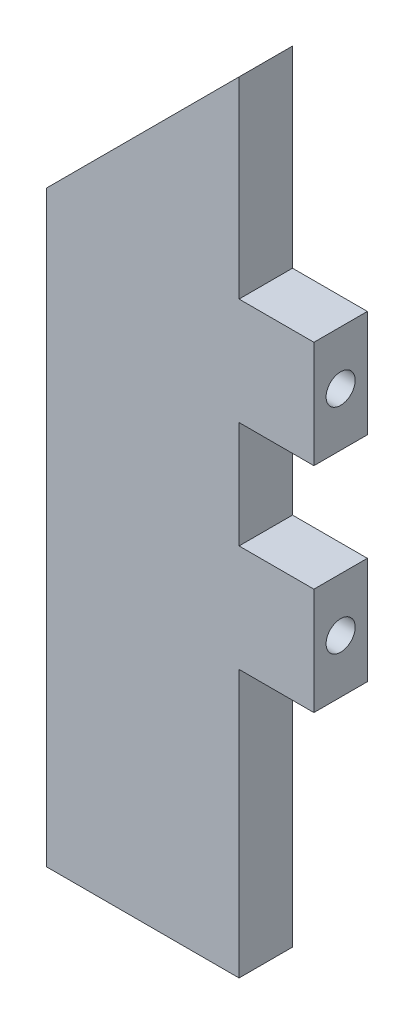
SolidWorks part; units mm, degrees
ref_plane "Front Plane" through (0, 0, 0) normal (0, 0, 1) x (1, 0, 0)
ref_plane "Top Plane" through (0, 0, 0) normal (0, 1, 0) x (1, 0, 0)
ref_plane "Right Plane" through (0, 0, 0) normal (1, 0, 0) x (0, 0, -1)
sketch "Sketch1" plane through (0, 0, 0) normal (0, 1, 0) x (1, 0, 0)
  line L1 (0, 0) -> (31.75, 0)
  line L2 (0, 0) -> (0, 6.35)
  line L3 (0, 6.35) -> (31.75, 6.35)
  line L4 (31.75, 0) -> (31.75, 6.35)
  dimension "D1" = 31.75
  dimension "D2" = 6.35
extrude "Boss-Extrude1" add sketch "Sketch1" along normal blind 101.6
chamfer "Chamfer1" distance 31.75 angle 45 1 edges at (0, 101.6, -3.175)
hole_wizard "#8-32 Tapped Hole1" positions "Sketch2" profile "Sketch3" tap size "#8-32" standard "ANSI Inch"
sketch "Sketch2" plane through (31.75, 0, 0) normal (1, 0, 0) x (0, 0, -1)
  line L0 (0, 0) -> (6.35, 0) construction
  line L1 (0, 101.6) -> (0, 0) construction
  point P0 (3.175, 63.5)
  point P2 (3.175, 38.1)
  dimension "D1" = 63.5
  dimension "D2" = 38.1
  dimension "D3" = 3.175
sketch "Sketch3" plane through (31.75, 63.5, -3.175) normal (0, 1, 0) x (0, 0, -1)
  line L0 (0, 0) -> (0, 7.3878)
  line L1 (0, 7.3878) -> (1.7272, 6.35)
  line L2 (1.7272, 6.35) -> (1.7272, 0)
  line L5 (1.7272, 0) -> (0, 0)
  line L10 (0, 7.3878) -> (-1.7272, 6.35) construction
  line L11 (0, -6.35) -> (0, 107.95) construction
  dimension "Tap Drill Dia." = 3.4544
  dimension "Tap Drill Depth" = 6.35
  dimension "Drill Angle" = 118
cosmetic thread "Hole Thread1" parameters "D1"=8.382, "D2"=4.1656
cosmetic thread "Hole Thread2" parameters "D1"=8.382, "D2"=4.1656
sketch "Sketch4" plane through (0, 0, 0) normal (0, 0, 1) x (1, 0, 0)
  line L0 (0, 0) -> (31.75, 0) construction
  line L1 (22.86, 0) -> (31.75, 0)
  line L2 (22.86, 0) -> (22.86, 31.75)
  line L3 (22.86, 31.75) -> (31.75, 31.75)
  line L4 (31.75, 0) -> (31.75, 31.75)
  line L5 (31.75, 101.6) -> (31.75, 0) construction
  line L7 (31.75, 44.45) -> (22.86, 44.45)
  line L8 (31.75, 44.45) -> (31.75, 57.15)
  line L9 (31.75, 57.15) -> (22.86, 57.15)
  line L10 (22.86, 44.45) -> (22.86, 57.15)
  line L11 (31.75, 69.85) -> (22.86, 69.85)
  line L12 (31.75, 69.85) -> (31.75, 101.6)
  line L13 (31.75, 101.6) -> (22.86, 101.6)
  line L14 (22.86, 69.85) -> (22.86, 101.6)
  point P16 (0, 0)
  dimension "D1" = 8.89
  dimension "D2" = 31.75
  dimension "D3" = 12.7
  dimension "D4" = 12.7
  dimension "D5" = 12.7
extrude "Cut-Extrude1" cut sketch "Sketch4" against normal through all
